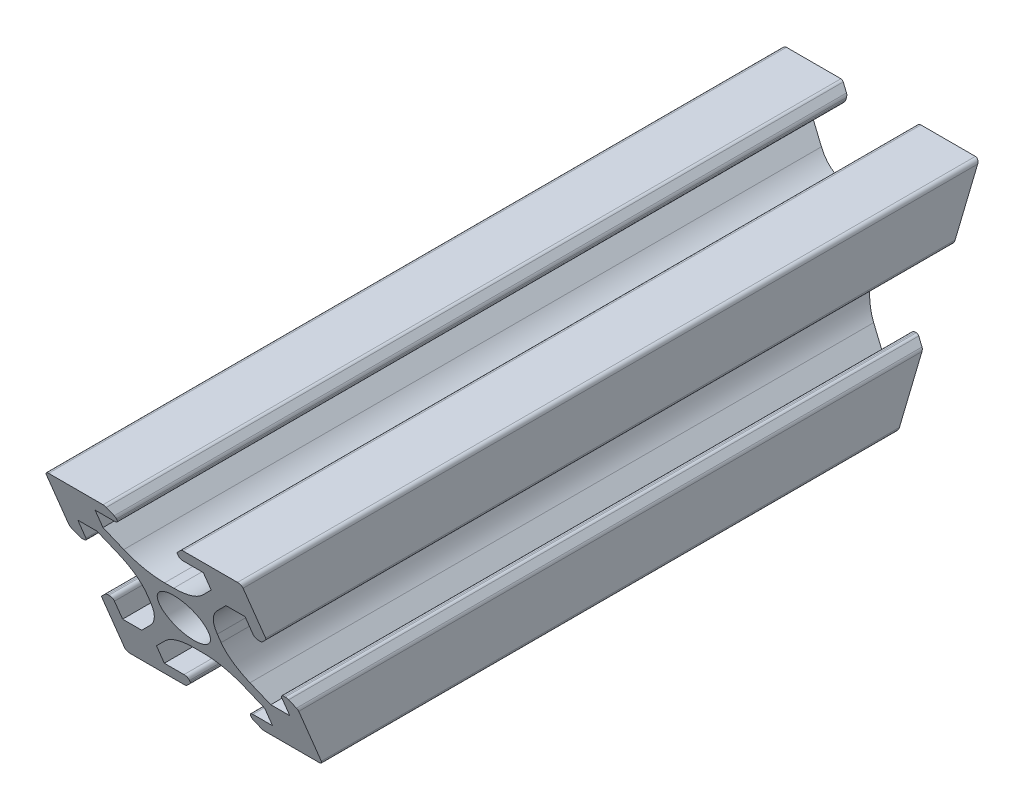
SolidWorks part; units mm, degrees
material "6063-T83"
ref_plane "Plano frontal" through (0, 0, 0) normal (0, 0, 1) x (1, 0, 0)
ref_plane "Plano superior" through (0, 0, 0) normal (0, 1, 0) x (1, 0, 0)
ref_plane "Plano direito" through (0, 0, 0) normal (1, 0, 0) x (0, 0, -1)
sketch "Esboço1" plane through (0, 0, 0) normal (0, 0, 1) x (1, 0, 0)
  line L0 (-9.0343, 3.1) -> (-8.9, 3.1)
  line L3 (-10, 10) -> (-4.0657, 10)
  line L5 (-10, -10) -> (10, 10) construction
  line L6 (-10, 10) -> (10, -10) construction
  line L7 (-8.5, 3.5) -> (-8.5, 5.5)
  line L8 (-10, 0) -> (10, 0) construction
  line L9 (0, 10) -> (0, -10) construction
  line L12 (-8.5, 5.5) -> (-6.5607, 5.5)
  line L15 (-6.5607, 5.5) -> (-5.0645, 4.0038)
  line L16 (-3.6, 0.4683) -> (-3.6, 0)
  line L17 (-0.4683, 3.6) -> (0, 3.6)
  line L18 (-5.5, 6.5607) -> (-4.0038, 5.0645)
  line L21 (-5.5, 8.5) -> (-5.5, 6.5607)
  line L24 (-3.5, 8.5) -> (-5.5, 8.5)
  line L25 (-3.1, 9.0343) -> (-3.1, 8.9)
  line L44 (-10, 4.0657) -> (-10, 10)
  line L45 (-9.8828, 3.7828) -> (-9.3172, 3.2172)
  line L46 (-3.7828, 9.8828) -> (-3.2172, 9.3172)
  line L47 (-3.6, 0) -> (-2.5, 0)
  line L48 (0, 3.6) -> (0, 2.5)
  arc A0 (-3.5, 8.5) -> (-3.1, 8.9) centre (-3.5, 8.9) ccw
  arc A1 (-3.7828, 9.8828) -> (-4.0657, 10) centre (-4.0657, 9.6) ccw
  arc A2 (-10, 4.0657) -> (-9.8828, 3.7828) centre (-9.6, 4.0657) ccw
  arc A3 (-8.5, 3.5) -> (-8.9, 3.1) centre (-8.9, 3.5) cw
  arc A4 (-3.2172, 9.3172) -> (-3.1, 9.0343) centre (-3.5, 9.0343) cw
  arc A5 (-9.3172, 3.2172) -> (-9.0343, 3.1) centre (-9.0343, 3.5) ccw
  arc A6 (-3.6, 0.4683) -> (-5.0645, 4.0038) centre (-8.6, 0.4683) ccw
  arc A7 (-4.0038, 5.0645) -> (-0.4683, 3.6) centre (-0.4683, 8.6) ccw
  circle A8 centre (0, 0) radius 2.5
  point P6 (-10, 3.1)
  point P28 (-3.1, 8.5)
  point P31 (-3.1, 10)
  point P33 (-3.9, 10)
  point P36 (-10, 3.9)
  point P39 (-8.5, 3.1)
  point P42 (-3.1, 9.2)
  point P45 (-9.2, 3.1)
  point P48 (-3.6, 2.5393)
  point P51 (-2.5393, 3.6)
  dimension "D5" = 10
  dimension "D9" = 0.4
  dimension "D10" = 0.4
  dimension "D11" = 5
  dimension "D12" = 5
  dimension "D13" = 5
  dimension "D1" = 6.9
  dimension "D2" = 1.5
  dimension "D3" = 3.6
  dimension "D4" = 1.5
  dimension "D6" = 2.4
  dimension "D7" = 3.6
  dimension "D8" = 45
extrude "Ressalto-extrusão1" add sketch "Esboço1" along normal blind 75 contours A4 A3 L3 A0 L17 L18 L21 L24 L25 L0 L7 L12 L15 L16 region at (-5.9987, 5.9987, 0)
sketch "Esboço3" plane through (0, 0, 0) normal (1, 0, 0) x (0, 0, -1)
  line L0 (0, 0) -> (-75, 0) construction
  line L1 (-75, 2.5) -> (-75, 0) construction
pattern_circular "PadrãoCircular1" count 4 every 90 about axis through (0, 0, 0) along (0, 0, 1) of "Ressalto-extrusão1"
fillet "Filete1" radius 0.4 4 edges at (-10, -10, 37.5) (-10, 10, 37.5) (10, -10, 37.5) (10, 10, 37.5)
ref_plane "Plane1" through (0, 0, 37.5) normal (0, 0, 1) x (1, 0, 0)
sketch "Sketch3" plane through (10, 0, 0) normal (1, 0, 0) x (0, 0, -1)
  line L0 (-37.5, 9.6) -> (-37.5, -9.6) construction
  line L1 (0, 9.6) -> (-75, 9.6) construction
  line L2 (-75, -9.6) -> (0, -9.6) construction
  line L3 (0, 0) -> (-75, 0) construction
  line L4 (-75, 2.5) -> (-75, -2.5) construction
  circle A0 centre (-27.5, 0) radius 2
  circle A1 centre (-47.5, 0) radius 2
  dimension "D1" = 4
  dimension "D2" = 20
extrude "Cut-Extrude2" cut sketch "Sketch3" against normal through all
sketch "Sketch1" plane through (-10, 0, 0) normal (-1, 0, 0) x (0, 0, 1)
  line L0 (0, 10) -> (0, -10)
  line L1 (0, 0) -> (75, 0) construction
  line L2 (0, 10) -> (8.2843, -10)
  line L3 (0, -10) -> (8.2843, -10)
  line L4 (37.5, 9.6) -> (37.5, -9.6) construction
  line L5 (75, 9.6) -> (0, 9.6) construction
  line L6 (0, -9.6) -> (75, -9.6) construction
  line L7 (75, 9.6) -> (75, -9.6)
  line L8 (75, -10) -> (66.7157, -10)
  line L9 (75, 10) -> (66.7157, -10)
  line L10 (75, 10) -> (75, -10)
  line M5 (75, 4.0657) -> (75, 9.6)
  line M6 (75, 9.6) -> (0, 9.6)
  line M7 (0, 9.6) -> (0, 4.0657)
  line M8 (0, 4.0657) -> (75, 4.0657)
  dimension "D1" = 10
  dimension "D2" = 22.5
extrude "Cut-Extrude1" cut sketch "Sketch1" against normal through all contours L0 L3 L2 M8 | L2 M6 M7 M8 | L9 M6 M8 M5 | L10 L7 L9 L8 M8 | L10 L9 M6 | L2 L0 M6 region at (-10, 9.7333, 0.0552) region at (-10, 6.027, 0.8228) region at (-10, -4.2386, 2.9489) region at (-10, 6.027, 74.1772) region at (-10, 9.7333, 74.9448) region at (-10, -4.2386, 72.0511)
